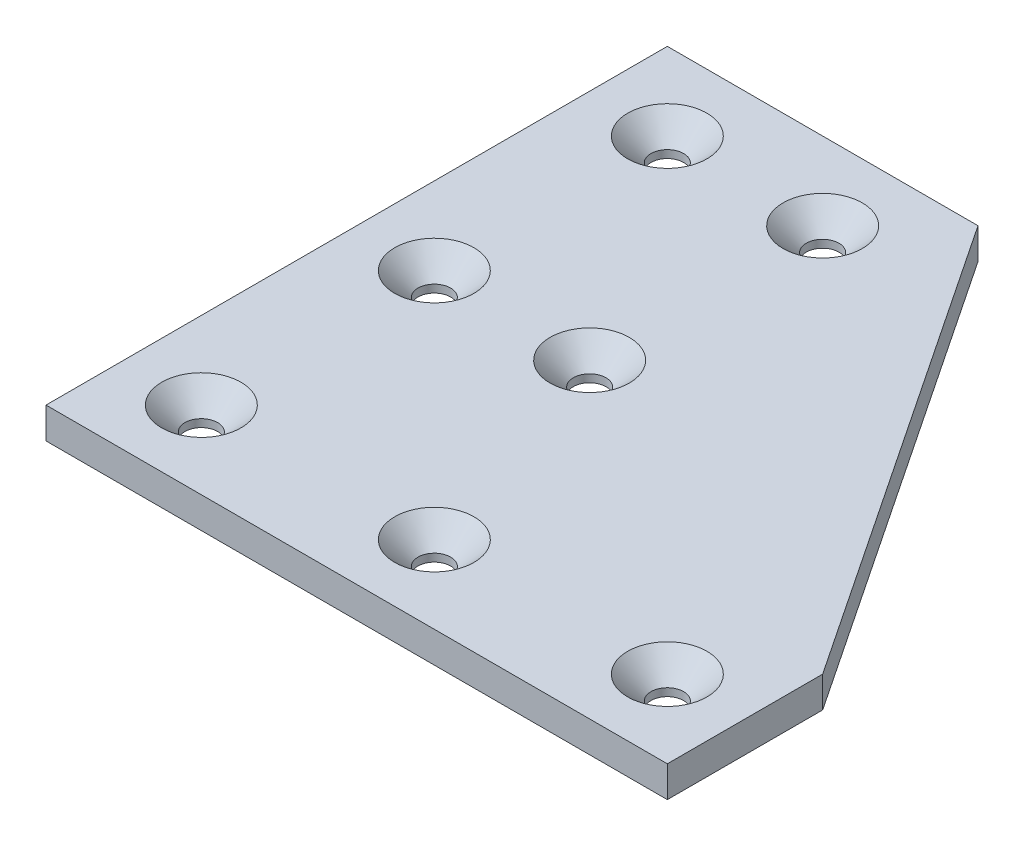
SolidWorks part; units mm, degrees
material "Aluminum 6105-T5"
ref_plane "Front Plane" through (0, 0, 0) normal (0, 0, 1) x (1, 0, 0)
ref_plane "Top Plane" through (0, 0, 0) normal (0, 1, 0) x (1, 0, 0)
ref_plane "Right Plane" through (0, 0, 0) normal (1, 0, 0) x (0, 0, -1)
sketch "Sketch1" plane through (0, 0, 0) normal (0, 1, 0) x (1, 0, 0)
  line L0 (0, 0) -> (80, 0)
  line L1 (80, 0) -> (80, 20)
  line L2 (80, 20) -> (40, 80)
  line L3 (40, 80) -> (0, 80)
  line L4 (0, 80) -> (0, 0)
  point P8 (0, 80)
  point P11 (40, 80)
  point P14 (80, 20)
  point P17 (80, 0)
  point P20 (0, 0)
  dimension "D1" = 80
  dimension "D2" = 80
  dimension "D3" = 20
  dimension "D4" = 40
extrude "Boss-Extrude1" add sketch "Sketch1" along normal blind 4
sketch "Sketch2" plane through (0, 4, 0) normal (0, 1, 0) x (1, 0, 0)
  line L0 (0, 0) -> (80, 0) construction
  line L1 (0, 80) -> (0, 0) construction
  line L2 (80, 0) -> (80, 20) construction
  line L3 (40, 80) -> (0, 80) construction
  circle A0 centre (10, 10) radius 2.1
  circle A1 centre (40, 10) radius 2.1
  circle A2 centre (70, 10) radius 2.1
  circle A4 centre (30, 40) radius 2.1
  circle A5 centre (30, 70) radius 2.1
  circle A6 centre (10, 40) radius 2.1
  circle A7 centre (10, 70) radius 2.1
  circle A8 centre (30, 10) radius 2.1 [skipped]
  dimension "D1" = 4.2
  dimension "D3" = 3
  dimension "D2" = 10
  dimension "10" = 10
  dimension "D4" = 10
  dimension "D7" = 10
  dimension "D8" = 10
  dimension "D9" = 20
  dimension "D5" = 2
  dimension "D6" = 3
extrude "Cut-Extrude1" cut sketch "Sketch2" against normal blind 4
chamfer "Chamfer1" distance 3 angle 45 7 edges at (70, 4, -7.9) (40, 4, -7.9) (10, 4, -7.9) (30, 4, -37.9) (10, 4, -37.9) (30, 4, -67.9) (10, 4, -67.9)
fillet "Fillet1" [suppressed] radius 1
